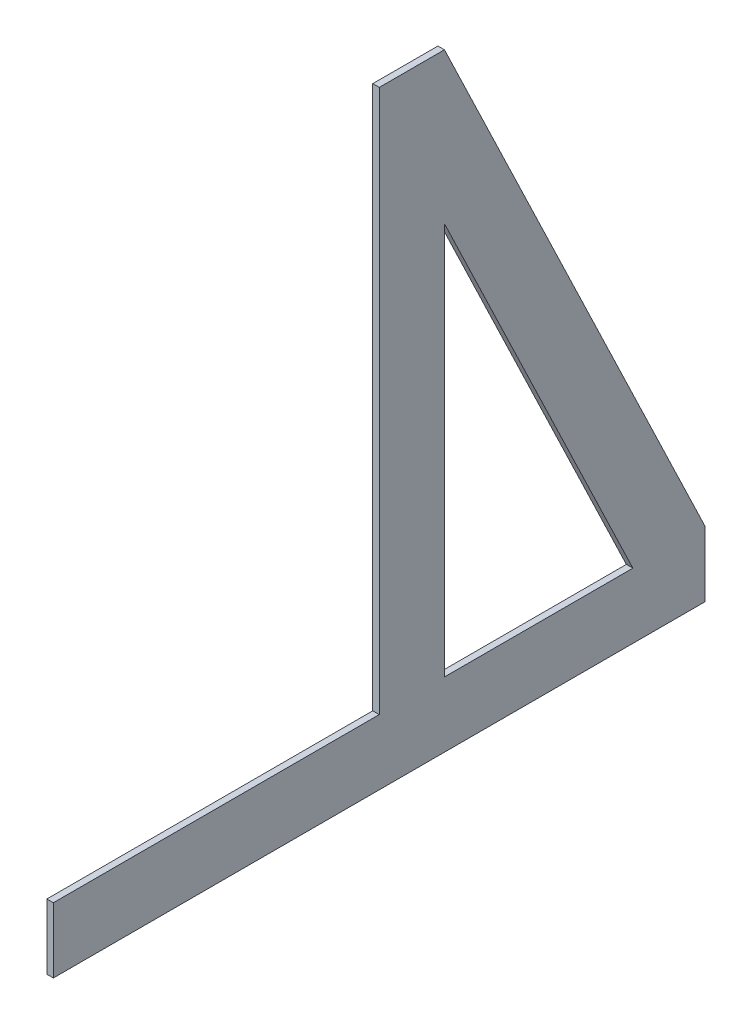
SolidWorks part; units mm, degrees
material "Клен"
ref_plane "Спереди" through (0, 0, 0) normal (0, 0, 1) x (1, 0, 0)
ref_plane "Сверху" through (0, 0, 0) normal (0, 1, 0) x (1, 0, 0)
ref_plane "Справа" through (0, 0, 0) normal (1, 0, 0) x (0, 0, -1)
sketch "боковина" plane through (0, 0, 0) normal (1, 0, 0) x (0, 0, -1)
  line L0 (-593.8462, -224.4615) -> (6.1538, -224.4615)
  line L1 (6.1538, -224.4615) -> (6.1538, -164.4615)
  line L2 (6.1538, -164.4615) -> (-233.8462, 335.5385)
  line L3 (-233.8462, 335.5385) -> (-293.8462, 335.5385)
  line L4 (-293.8462, 335.5385) -> (-293.8462, -164.4615)
  line L5 (-293.8462, -164.4615) -> (-593.8462, -164.4615)
  line L6 (-593.8462, -164.4615) -> (-593.8462, -224.4615)
  line L7 (-233.8462, -164.4615) -> (-60.4002, -164.4615)
  line L8 (-60.4002, -164.4615) -> (-233.8462, 196.8842)
  line L9 (-233.8462, 196.8842) -> (-233.8462, -164.4615)
  dimension "D1" = 60
  dimension "D2" = 60
  dimension "D3" = 600
  dimension "D5" = 60
  dimension "D6" = 300
  dimension "D7" = 60
  dimension "D8" = 60
  dimension "D4" = 500
extrude "Бобышка-боковина" add sketch "боковина" along normal blind 6
equation "\"D2@боковина\" = \"bottom_line\""
equation "\"D5@боковина\" = \"bottom_line\""
equation "\"D7@боковина\" = \"bottom_line\""
equation "\"D8@боковина\" = \"bottom_line\""
equation "\"sheet_thickness\"= 6"
equation "\"bottom_line\"= 60"
equation "\"width_space\"= 500"
